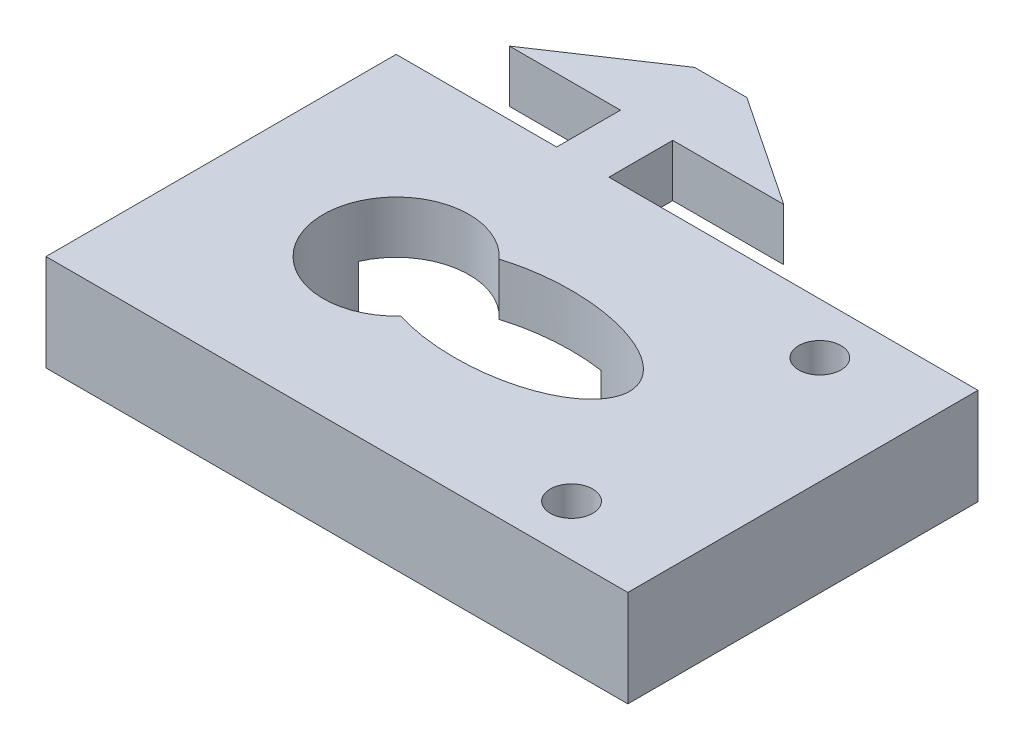
SolidWorks part; units mm, degrees
ref_plane "Front" through (0, 0, 0) normal (0, 0, 1) x (1, 0, 0)
ref_plane "Top" through (0, 0, 0) normal (0, 1, 0) x (1, 0, 0)
ref_plane "Right" through (0, 0, 0) normal (1, 0, 0) x (0, 0, -1)
sketch "Sketch1" plane through (0, 0, 0) normal (0, 1, 0) x (1, 0, 0)
  line L0 (-1.7907, 2.1875) -> (-9.398, 2.1875)
  line L2 (-1.7907, -2.1875) -> (-1.7907, 2.1875)
  line L4 (1.7907, -2.1875) -> (1.7907, 2.1875)
  line L7 (-9.398, 2.1875) -> (-1.7907, 7.2675)
  line L8 (-1.7907, 7.2675) -> (1.7907, 7.2675)
  line L9 (1.7907, 7.2675) -> (9.398, 2.1875)
  line L10 (9.398, 2.1875) -> (1.7907, 2.1875)
  line L11 (1.7907, -2.1875) -> (27.088, -2.1875)
  line L12 (-1.7907, -2.1875) -> (-12.79, -2.1875)
  line L13 (-12.79, -2.1875) -> (-12.79, -26.1875)
  line L14 (-12.79, -26.1875) -> (27.088, -26.1875)
  line L15 (27.088, -26.1875) -> (27.088, -2.1875)
  line L16 (27.088, -2.1875) -> (1.7907, -2.1875)
  point P0 (0, 0)
  point P17 (0, 7.2675)
  point P24 (1.7907, 0)
  dimension "D1" = 18.796
  dimension "D2" = 3.5814
  dimension "D3" = 39.878
  dimension "D4" = 24
  dimension "D5" = 5.08
  dimension "D6" = 12.79
  dimension "D7" = 4.375
extrude "Boss-Extrude1" add sketch "Sketch1" along normal blind 3.5814 contours L14 L15 L11 L4 L10 L9 L8 L7 L0 L2 L12 L13 region at (6.6455, 0, 12.9592)
ref_plane "Plane1" through (0, 1.7907, 0) normal (0, 1, 0) x (1, 0, 0)
sketch "Sketch7" plane through (0, 0, 0) normal (0, 1, 0) x (1, 0, 0)
  line L1 (-12.79, -2.1875) -> (27.088, -2.1875)
  line L2 (-12.79, -2.1875) -> (-12.79, -26.1875)
  line L3 (-12.79, -26.1875) -> (27.088, -26.1875)
  line L4 (27.088, -2.1875) -> (27.088, -26.1875)
extrude "Boss-Extrude2" add sketch "Sketch7" along normal blind 3.035 and the other way blind 3.035
sketch "Sketch5" plane through (0, 3.5814, 0) normal (0, 1, 0) x (1, 0, 0)
  line L0 (-12.79, -2.1875) -> (-12.79, -26.1875) construction
  line L1 (-12.79, -14.1875) -> (27.088, -14.1875) construction
  line L2 (27.088, -26.1875) -> (27.088, -2.1875) construction
  circle A0 centre (-0.79, -14.1875) radius 5
  circle A1 centre (19.738, -22.6965) radius 1.45
  circle A2 centre (19.738, -5.6785) radius 1.45
  ellipse E0 centre (7.21, -14.1875) end of major axis (-0.79, -14.1875) minor radius 4
  point P5 (-12.79, -14.1875)
  dimension "D2" = 10
  dimension "D6" = 2.9
  dimension "D1" = 12
  dimension "D3" = 8
  dimension "D4" = 16
  dimension "D5" = 17.018
  dimension "D7" = 7.35
extrude "Cut-Extrude3" cut sketch "Sketch5" against normal through all both and the other way through all contours A0 L1 E0 | E0 L1 A0 | A0 L1 E0 | L1 A0 E0 | L1 E0 A0 | L1 A0 E0 | A1 | A2 region at (1.9147, 3.5814, 12.8793) region at (-1.952, 3.5814, 16.6592) region at (1.9147, 3.5814, 15.4957) region at (-1.952, 3.5814, 11.7158) region at (8.8346, 3.5814, 12.3704) region at (8.8346, 3.5814, 16.0046) region at (19.738, 3.5814, 22.6965)
ref_plane "Plane2" through (0, 0, -17.2675) normal (0, 0, -1) x (-1, 0, 0)
sketch "Sketch8" plane through (0, 0, 2.1875) normal (0, 0, -1) x (-1, 0, 0)
  line L0 (-27.088, -3.035) -> (12.79, -3.035) construction
  line L1 (-9.398, 0) -> (9.398, 0)
  line L2 (-9.398, 0) -> (-9.398, -3.035)
  line L3 (-9.398, -3.035) -> (9.398, -3.035)
  line L4 (9.398, 0) -> (9.398, -3.035)
  line L5 (-9.398, 3.5814) -> (-9.398, 0) construction
  line L6 (9.398, 3.5814) -> (9.398, 0) construction
  line L7 (-1.7907, 0) -> (1.7907, 0) construction
extrude "Cut-Extrude4" cut sketch "Sketch8" against normal blind 10
